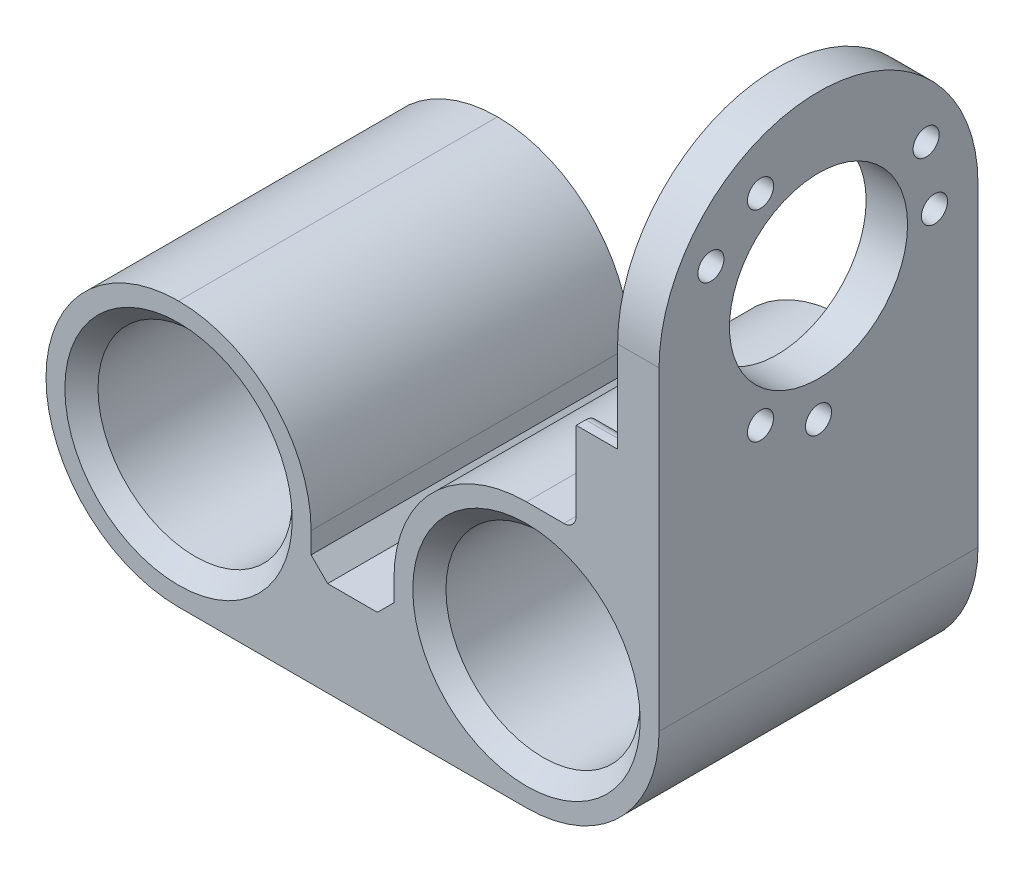
SolidWorks part; units mm, degrees
material "ABS"
ref_plane "Front Plane" through (0, 0, 0) normal (0, 0, 1) x (1, 0, 0)
ref_plane "Top Plane" through (0, 0, 0) normal (0, 1, 0) x (1, 0, 0)
ref_plane "Right Plane" through (0, 0, 0) normal (1, 0, 0) x (0, 0, -1)
sketch "Sketch1" plane through (0, 0, 0) normal (0, 0, 1) x (1, 0, 0)
  line L1 (0, 0) -> (74, 0)
  line L2 (0, 0) -> (0, 32)
  line L3 (0, 32) -> (74, 32)
  line L4 (74, 0) -> (74, 32)
  circle A0 centre (16, 16) radius 11.725
  circle A1 centre (58, 16) radius 11.725
  point P9 (0, 16)
  dimension "D1" = 23.45
  dimension "D2" = 23.45
  dimension "D3" = 42
  dimension "D4" = 16
  dimension "D5" = 16
  dimension "D6" = 16
  dimension "D7" = 16
extrude "Boss-Extrude1" add sketch "Sketch1" along normal blind 38.5
sketch "Sketch2" plane through (74, 0, 0) normal (1, 0, 0) x (0, 0, -1)
  line L0 (-19.25, 54) -> (-5.25, 54) construction
  line L1 (-19.25, 73.25) -> (-19.25, 34.75) construction
  line L2 (-38.5, 32) -> (0, 32) construction
  line L3 (-19.25, 54) -> (-6.2596, 61.5) construction
  line L4 (0, 32) -> (0, 54)
  line L5 (-38.5, 32) -> (-38.5, 54)
  line L7 (-38.5, 32) -> (0, 32)
  line L8 (-38.5, 32) -> (-38.5, 0)
  line L9 (-38.5, 0) -> (0, 0)
  line L10 (0, 32) -> (0, 0)
  circle A0 centre (-19.25, 54) radius 19.25
  circle A1 centre (-19.25, 54) radius 14 construction
  circle A2 centre (-19.25, 54) radius 15 construction
  circle A4 centre (-6.2596, 61.5) radius 1.575
  circle A5 centre (-5.25, 54) radius 1.575
  circle A10 centre (-19.25, 54) radius 10.75
  circle A11 centre (-26.25, 41.8756) radius 1.575
  circle A12 centre (-19.25, 39) radius 1.575
  circle A13 centre (-26.25, 66.1244) radius 1.575
  circle A14 centre (-32.2404, 61.5) radius 1.575
  point P11 (-19.25, 32)
  point P26 (-19.25, 54)
  point P32 (-19.25, 54)
  line M13 (0, 32) -> (-38.5, 32)
  dimension "D1" = 38.5
  dimension "D2" = 28
  dimension "D3" = 30
  dimension "D4" = 90
  dimension "D6" = 3
  dimension "D7" = 22
  dimension "D8" = 21.5
  dimension "D9" = 3.15
  dimension "D5" = 30
extrude "Boss-Extrude2" add sketch "Sketch2" against normal blind 5 contours A0 L5 L4 M13 | A0 A13 A14 A11 A12 A5 A4
sketch "Sketch3" plane through (69, 0, 0) normal (-1, 0, 0) x (0, 0, 1)
  line L0 (0, 32) -> (0, 54)
  line L1 (0, 32) -> (38.5, 32)
  line L2 (38.5, 32) -> (38.5, 54)
  line L3 (0, 43) -> (38.5, 43)
  circle A0 centre (19.25, 54) radius 20.5
  point P13 (0, 0)
  point P14 (0, 0)
  point P15 (38.5, 54)
  point P17 (0, 54)
  dimension "D1" = 41
extrude "Boss-Extrude3" add sketch "Sketch3" along normal blind 5
sketch "Sketch4" plane through (0, 0, 0) normal (0, 0, -1) x (-1, 0, 0)
  line L0 (-46.2967, 15.2873) -> (-27.7033, 15.2873) construction
  line L1 (-7.8067, 7.6127) -> (-66.1933, 7.6127) construction
  line L2 (-37, 15.2873) -> (-37, 7.6127) construction
  line L3 (-46.275, 16) -> (-27.725, 16) construction
  line L4 (-42, 11.45) -> (-32, 11.45)
  line L5 (-42, -13.55) -> (-32, -13.55)
  line L6 (-42, -13.55) -> (-42, 36.45)
  line L7 (-42, 36.45) -> (-32, 36.45)
  line L8 (-32, -13.55) -> (-32, 36.45)
  line L9 (-42, -13.55) -> (-32, 36.45) construction
  line L10 (-42, 36.45) -> (-32, -13.55) construction
  circle A0 centre (-58, 16) radius 11.725 construction
  circle A1 centre (-16, 16) radius 11.725 construction
  point P13 (-37, 11.45)
  dimension "D1" = 10
  dimension "D2" = 25
extrude "Cut-Extrude1" cut sketch "Sketch4" against normal through all both and the other way through all
sketch "Sketch5" plane through (0, 11.45, 0) normal (0, 1, 0) x (1, 0, 0)
  line L0 (32, 0) -> (32, -38.5)
  line L6 (42, 0) -> (32, 0)
  circle A0 centre (37, -19.25) radius 1.525
  point P2 (37, 0)
  point P4 (32, -19.25)
  dimension "D1" = 3.05
extrude "Cut-Extrude2" cut sketch "Sketch5" against normal blind 8 and the other way through all contours A0
fillet "Fillet8" radius 16 5 edges at (42, 32, 19.25) (32, 32, 19.25) (0, 32, 19.25) (0, 0, 19.25) (74, 0, 19.25)
fillet "Fillet9" radius 1.5 3 edges at (66.5, 43, 1.9512) (66.5, 43, 36.5488) (64, 32, 19.25)
fillet "Fillet10" radius 2 6 edges at (69.725, 16, 38.5) (69.725, 16, 0) (27.725, 16, 38.5) (27.725, 16, 0) (32, 11.45, 19.25) (42, 11.45, 19.25) profile chamfer
